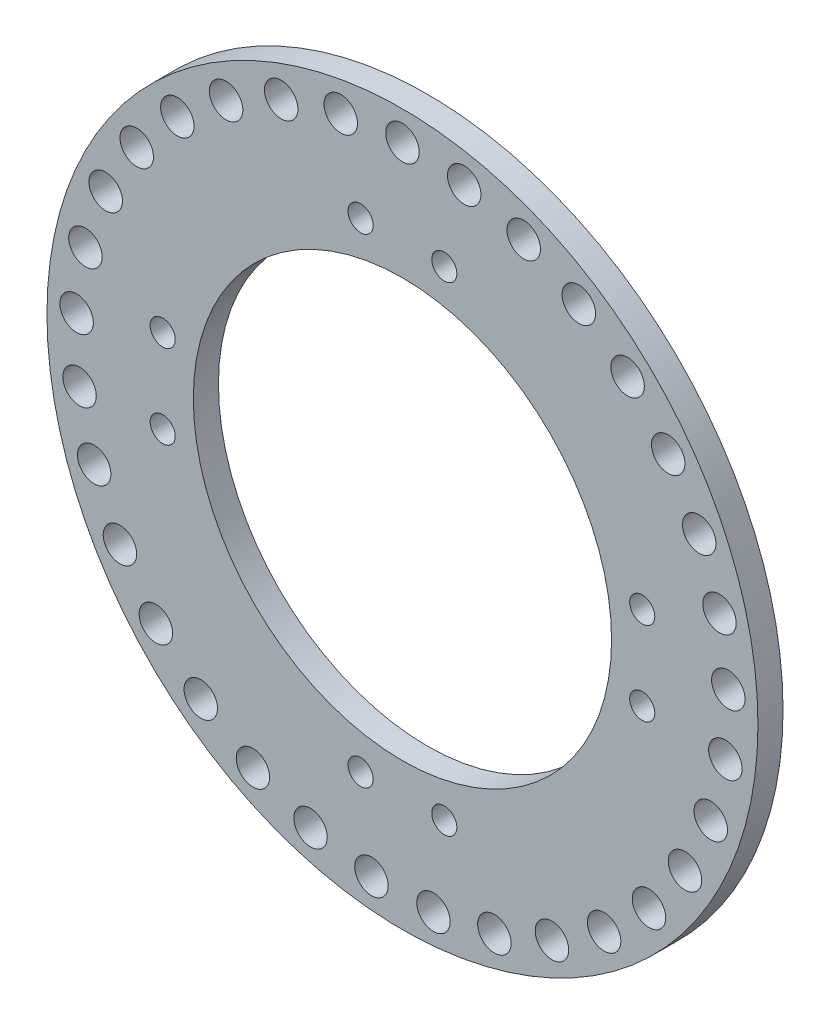
SolidWorks part; units mm, degrees
ref_plane "Front Plane" through (0, 0, 0) normal (0, 0, 1) x (1, 0, 0)
ref_plane "Top Plane" through (0, 0, 0) normal (0, 1, 0) x (1, 0, 0)
ref_plane "Right Plane" through (0, 0, 0) normal (1, 0, 0) x (0, 0, -1)
sketch "Sketch1" plane through (0, 0, 0) normal (0, 0, 1) x (1, 0, 0)
  line L0 (0, 0) -> (0, 76.7228) construction
  line L1 (-5, 28.6654) -> (7.5438, 28.6654) construction
  line L2 (-1.65, 27.0934) -> (1.65, 27.0934) construction
  line L3 (-1.65, 27.0934) -> (-1.65, 38.3614) construction
  line L4 (-1.65, 38.3614) -> (1.65, 38.3614) construction
  line L5 (1.65, 27.0934) -> (1.65, 38.3614) construction
  circle A0 centre (0, 0) radius 42.5
  circle A1 centre (0, 0) radius 25
  circle A2 centre (-5, 28.6654) radius 1.5
  circle A3 centre (5, 28.6654) radius 1.5
  circle A4 centre (28.6654, 5) radius 1.5
  circle A5 centre (28.6654, -5) radius 1.5
  circle A6 centre (5, -28.6654) radius 1.5
  circle A7 centre (-5, -28.6654) radius 1.5
  circle A8 centre (-28.6654, -5) radius 1.5
  circle A9 centre (-28.6654, 5) radius 1.5
  point P7 (0, 42.5)
  point P10 (0, 38.3614)
  dimension "D1" = 85
  dimension "D2" = 50
  dimension "D3" = 3
  dimension "D4" = 3.3
  dimension "D5" = 5
  dimension "D6" = 4
extrude "Boss-Extrude1" add sketch "Sketch1" along normal blind 3
sketch "Sketch2" plane through (0, 0, 3) normal (0, 0, 1) x (1, 0, 0)
  line L0 (0, 0) -> (0, 46.0615) construction
  circle A0 centre (0, 39) radius 2
  circle A1 centre (0, 0) radius 42.5 construction
  point P5 (0, 42.5)
  dimension "D1" = 3.5
extrude "Cut-Extrude1" cut sketch "Sketch2" against normal through all
pattern_circular "CirPattern1" count 33 over 360 about axis through (0, 0, 3) along (0, 0, -1) of "Cut-Extrude1"
sketch "Sketch3" plane through (0, 0, 3) normal (0, 0, 1) x (1, 0, 0)
  line L0 (3.7072, -38.8234) -> (0, 0) construction
  line L1 (0, 0) -> (-3.7072, -38.8234) construction
  dimension "D1" = 10.909
sketch "Sketch5" plane through (0, 0, 3) normal (0, 0, 1) x (1, 0, 0)
  line L0 (3.8898, 40.5) -> (-1.3229, 40.5) construction
  line L1 (0, 42.5) -> (3.8939, 42.5) construction
  circle A0 centre (0, 39) radius 2 construction
  circle A1 centre (0, 0) radius 42.5 construction
  circle A3 centre (0, 0) radius 42.5
  circle A4 centre (0, 0) radius 42.5 construction
  dimension "D1" = 0
  dimension "D2" = 2
